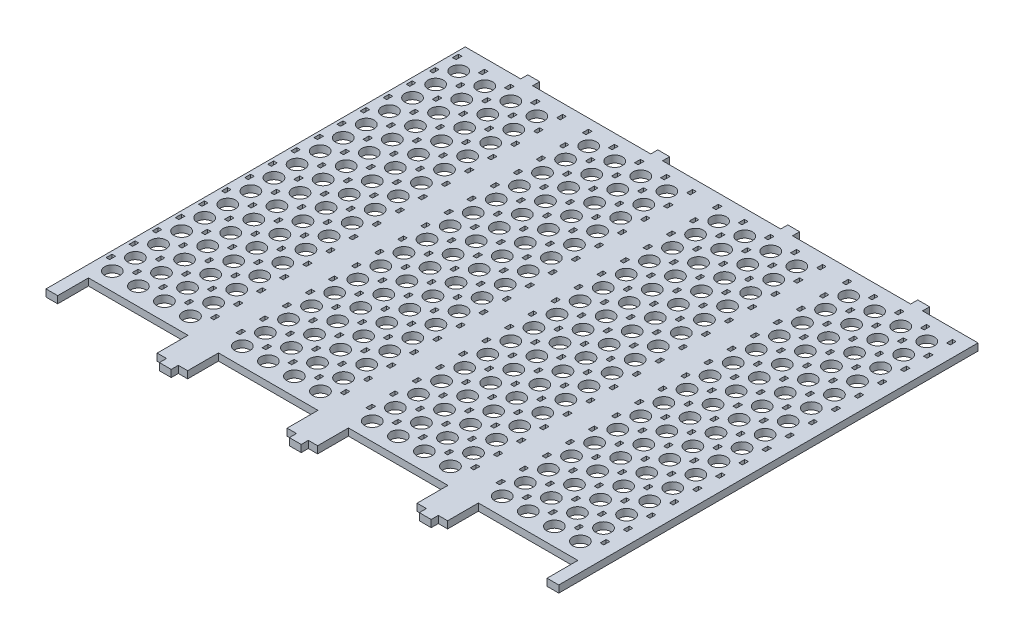
SolidWorks part; units mm, degrees
ref_plane "Front Plane" through (0, 0, 0) normal (0, 0, 1) x (1, 0, 0)
ref_plane "Top Plane" through (0, 0, 0) normal (0, 1, 0) x (1, 0, 0)
ref_plane "Right Plane" through (0, 0, 0) normal (1, 0, 0) x (0, 0, -1)
sketch "Sketch1" plane through (0, 0, 0) normal (0, 1, 0) x (1, 0, 0)
  line L1 (-216.5, -177) -> (216.5, -177)
  line L2 (-216.5, -177) -> (-216.5, 177)
  line L3 (-216.5, 177) -> (216.5, 177)
  line L4 (216.5, -177) -> (216.5, 177)
  line L5 (-216.5, -177) -> (216.5, 177) construction
  line L6 (-216.5, 177) -> (216.5, -177) construction
  point P0 (0, 0)
  dimension "D1" = 354
  dimension "D2" = 433
extrude "Boss-Extrude1" add sketch "Sketch1" along normal blind 6
sketch "Sketch2" plane through (0, 6, 0) normal (0, 1, 0) x (1, 0, 0)
  line L0 (-126.625, -177) -> (-131.125, -177) construction
  line L1 (-198.125, -177) -> (-202.625, -177) construction
  line L2 (-126.625, -177) -> (-131.125, -177)
  line L3 (-198.125, -177) -> (-202.625, -177) construction
  line L4 (-198.125, -177) -> (-131.125, -177) construction
  line L5 (-164.625, -177) -> (-164.625, -151) construction
  line L6 (-122.625, -177) -> (-122.625, -151)
  line L7 (-206.625, -177) -> (-206.625, -151)
  line L8 (-122.625, -177) -> (-206.625, -177)
  line L9 (-122.625, -151) -> (-206.625, -151)
  line M6 (-216.5, -177) -> (216.5, -177)
  dimension "D1" = 26
  dimension "D2" = 42
  dimension "D3" = 42
extrude "Cut-Extrude1" cut sketch "Sketch2" against normal up to next contours L6 L9 L7 M6 region at (-164.625, 6, 164)
pattern_linear "LPattern1" count 4 spacing 109.75 along (1, 0, 0) of "Cut-Extrude1"
sketch "Sketch3" plane through (0, 0, 177) normal (0, 0, 1) x (1, 0, 0)
  line L0 (-122.625, 6) -> (-96.875, 0) construction
  line L1 (-216.5, 6) -> (-206.625, 6) construction
  line L2 (-114.75, 0) -> (-104.75, 0)
  line L3 (-114.75, 0) -> (-114.75, 6)
  line L4 (-114.75, 6) -> (-104.75, 6)
  line L5 (-104.75, 0) -> (-104.75, 6)
  line L6 (-114.75, 0) -> (-104.75, 6) construction
  line L7 (-114.75, 6) -> (-104.75, 0) construction
  point P4 (-109.75, 3)
  dimension "D1" = 10
extrude "Boss-Extrude2" add sketch "Sketch3" along normal blind 6
pattern_linear "LPattern2" count 3 spacing 109.75 along (1, 0, 0) of "Boss-Extrude2"
sketch "Sketch4" plane through (0, 6, 0) normal (0, 1, 0) x (1, 0, 0)
  line L0 (-201.5, -151) -> (-201.5, -112.543) construction
  line L1 (-122.625, -151) -> (-206.625, -151) construction
  line L2 (-216.5, 177) -> (-216.5, -177) construction
  line L3 (-216.5, -136) -> (-147.9325, -136) construction
  circle A0 centre (-201.5, -136) radius 6.5
  circle A1 centre (-179.5, -136) radius 6.5
  circle A2 centre (-157.5, -136) radius 6.5
  circle A3 centre (-135.5, -136) radius 6.5
  circle A4 centre (-179.5, -116.5) radius 6.5
  circle A5 centre (-157.5, -116.5) radius 6.5
  circle A6 centre (-135.5, -116.5) radius 6.5
  circle A7 centre (-179.5, -97) radius 6.5
  circle A8 centre (-157.5, -97) radius 6.5
  circle A9 centre (-135.5, -97) radius 6.5
  circle A10 centre (-179.5, -77.5) radius 6.5
  circle A11 centre (-157.5, -77.5) radius 6.5
  circle A12 centre (-135.5, -77.5) radius 6.5
  circle A13 centre (-179.5, -58) radius 6.5
  circle A14 centre (-157.5, -58) radius 6.5
  circle A15 centre (-135.5, -58) radius 6.5
  circle A16 centre (-179.5, -38.5) radius 6.5
  circle A17 centre (-157.5, -38.5) radius 6.5
  circle A18 centre (-135.5, -38.5) radius 6.5
  circle A19 centre (-179.5, -19) radius 6.5
  circle A20 centre (-157.5, -19) radius 6.5
  circle A21 centre (-135.5, -19) radius 6.5
  circle A22 centre (-179.5, 0.5) radius 6.5
  circle A23 centre (-157.5, 0.5) radius 6.5
  circle A24 centre (-135.5, 0.5) radius 6.5
  circle A25 centre (-179.5, 20) radius 6.5
  circle A26 centre (-157.5, 20) radius 6.5
  circle A27 centre (-135.5, 20) radius 6.5
  circle A28 centre (-179.5, 39.5) radius 6.5
  circle A29 centre (-157.5, 39.5) radius 6.5
  circle A30 centre (-135.5, 39.5) radius 6.5
  circle A31 centre (-179.5, 59) radius 6.5
  circle A32 centre (-157.5, 59) radius 6.5
  circle A33 centre (-135.5, 59) radius 6.5
  circle A34 centre (-179.5, 78.5) radius 6.5
  circle A35 centre (-157.5, 78.5) radius 6.5
  circle A36 centre (-135.5, 78.5) radius 6.5
  circle A37 centre (-179.5, 98) radius 6.5
  circle A38 centre (-157.5, 98) radius 6.5
  circle A39 centre (-135.5, 98) radius 6.5
  circle A40 centre (-179.5, 117.5) radius 6.5
  circle A41 centre (-157.5, 117.5) radius 6.5
  circle A42 centre (-135.5, 117.5) radius 6.5
  circle A43 centre (-179.5, 137) radius 6.5
  circle A44 centre (-157.5, 137) radius 6.5
  circle A45 centre (-135.5, 137) radius 6.5
  circle A46 centre (-179.5, 156.5) radius 6.5
  circle A47 centre (-157.5, 156.5) radius 6.5
  circle A48 centre (-135.5, 156.5) radius 6.5
  circle A49 centre (-201.5, -116.5) radius 6.5
  circle A50 centre (-201.5, -97) radius 6.5
  circle A51 centre (-201.5, -77.5) radius 6.5
  circle A52 centre (-201.5, -58) radius 6.5
  circle A53 centre (-201.5, -38.5) radius 6.5
  circle A54 centre (-201.5, -19) radius 6.5
  circle A55 centre (-201.5, 0.5) radius 6.5
  circle A56 centre (-201.5, 20) radius 6.5
  circle A57 centre (-201.5, 39.5) radius 6.5
  circle A58 centre (-201.5, 59) radius 6.5
  circle A59 centre (-201.5, 78.5) radius 6.5
  circle A60 centre (-201.5, 98) radius 6.5
  circle A61 centre (-201.5, 117.5) radius 6.5
  circle A62 centre (-201.5, 137) radius 6.5
  circle A63 centre (-201.5, 156.5) radius 6.5
  dimension "D2" = 13
  dimension "D1" = 15
  dimension "D3" = 15
  dimension "D4" = 4
  dimension "D5" = 16
extrude "Cut-Extrude2" cut sketch "Sketch4" against normal up to next (6 mm away)
sketch "Sketch5" plane through (0, 6, 0) normal (0, 1, 0) x (1, 0, 0)
  line L0 (-201.5, -116.5) -> (-201.5, -136) construction
  line L1 (-214, -128.75) -> (-211, -128.75)
  line L2 (-214, -128.75) -> (-214, -123.75)
  line L3 (-214, -123.75) -> (-211, -123.75)
  line L4 (-211, -128.75) -> (-211, -123.75)
  line L5 (-214, -128.75) -> (-211, -123.75) construction
  line L6 (-214, -123.75) -> (-211, -128.75) construction
  line L7 (-192, -128.75) -> (-189, -128.75)
  line L8 (-192, -128.75) -> (-192, -123.75)
  line L9 (-192, -123.75) -> (-189, -123.75)
  line L10 (-189, -128.75) -> (-189, -123.75)
  line L11 (-192, -128.75) -> (-189, -123.75) construction
  line L12 (-192, -123.75) -> (-189, -128.75) construction
  line L13 (-170, -128.75) -> (-167, -128.75)
  line L14 (-170, -128.75) -> (-170, -123.75)
  line L15 (-170, -123.75) -> (-167, -123.75)
  line L16 (-167, -128.75) -> (-167, -123.75)
  line L17 (-170, -128.75) -> (-167, -123.75) construction
  line L18 (-170, -123.75) -> (-167, -128.75) construction
  line L19 (-148, -128.75) -> (-145, -128.75)
  line L20 (-148, -128.75) -> (-148, -123.75)
  line L21 (-148, -123.75) -> (-145, -123.75)
  line L22 (-145, -128.75) -> (-145, -123.75)
  line L23 (-148, -128.75) -> (-145, -123.75) construction
  line L24 (-148, -123.75) -> (-145, -128.75) construction
  line L25 (-126, -128.75) -> (-123, -128.75)
  line L26 (-126, -128.75) -> (-126, -123.75)
  line L27 (-126, -123.75) -> (-123, -123.75)
  line L28 (-123, -128.75) -> (-123, -123.75)
  line L29 (-126, -128.75) -> (-123, -123.75) construction
  line L30 (-126, -123.75) -> (-123, -128.75) construction
  line L31 (-192, -109.25) -> (-189, -109.25)
  line L32 (-192, -109.25) -> (-192, -104.25)
  line L33 (-192, -104.25) -> (-189, -104.25)
  line L34 (-189, -109.25) -> (-189, -104.25)
  line L35 (-192, -109.25) -> (-189, -104.25) construction
  line L36 (-192, -104.25) -> (-189, -109.25) construction
  line L37 (-170, -109.25) -> (-167, -109.25)
  line L38 (-170, -109.25) -> (-170, -104.25)
  line L39 (-170, -104.25) -> (-167, -104.25)
  line L40 (-167, -109.25) -> (-167, -104.25)
  line L41 (-170, -109.25) -> (-167, -104.25) construction
  line L42 (-170, -104.25) -> (-167, -109.25) construction
  line L43 (-148, -109.25) -> (-145, -109.25)
  line L44 (-148, -109.25) -> (-148, -104.25)
  line L45 (-148, -104.25) -> (-145, -104.25)
  line L46 (-145, -109.25) -> (-145, -104.25)
  line L47 (-148, -109.25) -> (-145, -104.25) construction
  line L48 (-148, -104.25) -> (-145, -109.25) construction
  line L49 (-126, -109.25) -> (-123, -109.25)
  line L50 (-126, -109.25) -> (-126, -104.25)
  line L51 (-126, -104.25) -> (-123, -104.25)
  line L52 (-123, -109.25) -> (-123, -104.25)
  line L53 (-126, -109.25) -> (-123, -104.25) construction
  line L54 (-126, -104.25) -> (-123, -109.25) construction
  line L55 (-192, -89.75) -> (-189, -89.75)
  line L56 (-192, -89.75) -> (-192, -84.75)
  line L57 (-192, -84.75) -> (-189, -84.75)
  line L58 (-189, -89.75) -> (-189, -84.75)
  line L59 (-192, -89.75) -> (-189, -84.75) construction
  line L60 (-192, -84.75) -> (-189, -89.75) construction
  line L61 (-170, -89.75) -> (-167, -89.75)
  line L62 (-170, -89.75) -> (-170, -84.75)
  line L63 (-170, -84.75) -> (-167, -84.75)
  line L64 (-167, -89.75) -> (-167, -84.75)
  line L65 (-170, -89.75) -> (-167, -84.75) construction
  line L66 (-170, -84.75) -> (-167, -89.75) construction
  line L67 (-148, -89.75) -> (-145, -89.75)
  line L68 (-148, -89.75) -> (-148, -84.75)
  line L69 (-148, -84.75) -> (-145, -84.75)
  line L70 (-145, -89.75) -> (-145, -84.75)
  line L71 (-148, -89.75) -> (-145, -84.75) construction
  line L72 (-148, -84.75) -> (-145, -89.75) construction
  line L73 (-126, -89.75) -> (-123, -89.75)
  line L74 (-126, -89.75) -> (-126, -84.75)
  line L75 (-126, -84.75) -> (-123, -84.75)
  line L76 (-123, -89.75) -> (-123, -84.75)
  line L77 (-126, -89.75) -> (-123, -84.75) construction
  line L78 (-126, -84.75) -> (-123, -89.75) construction
  line L79 (-192, -70.25) -> (-189, -70.25)
  line L80 (-192, -70.25) -> (-192, -65.25)
  line L81 (-192, -65.25) -> (-189, -65.25)
  line L82 (-189, -70.25) -> (-189, -65.25)
  line L83 (-192, -70.25) -> (-189, -65.25) construction
  line L84 (-192, -65.25) -> (-189, -70.25) construction
  line L85 (-170, -70.25) -> (-167, -70.25)
  line L86 (-170, -70.25) -> (-170, -65.25)
  line L87 (-170, -65.25) -> (-167, -65.25)
  line L88 (-167, -70.25) -> (-167, -65.25)
  line L89 (-170, -70.25) -> (-167, -65.25) construction
  line L90 (-170, -65.25) -> (-167, -70.25) construction
  line L91 (-148, -70.25) -> (-145, -70.25)
  line L92 (-148, -70.25) -> (-148, -65.25)
  line L93 (-148, -65.25) -> (-145, -65.25)
  line L94 (-145, -70.25) -> (-145, -65.25)
  line L95 (-148, -70.25) -> (-145, -65.25) construction
  line L96 (-148, -65.25) -> (-145, -70.25) construction
  line L97 (-126, -70.25) -> (-123, -70.25)
  line L98 (-126, -70.25) -> (-126, -65.25)
  line L99 (-126, -65.25) -> (-123, -65.25)
  line L100 (-123, -70.25) -> (-123, -65.25)
  line L101 (-126, -70.25) -> (-123, -65.25) construction
  line L102 (-126, -65.25) -> (-123, -70.25) construction
  line L103 (-192, -50.75) -> (-189, -50.75)
  line L104 (-192, -50.75) -> (-192, -45.75)
  line L105 (-192, -45.75) -> (-189, -45.75)
  line L106 (-189, -50.75) -> (-189, -45.75)
  line L107 (-192, -50.75) -> (-189, -45.75) construction
  line L108 (-192, -45.75) -> (-189, -50.75) construction
  line L109 (-170, -50.75) -> (-167, -50.75)
  line L110 (-170, -50.75) -> (-170, -45.75)
  line L111 (-170, -45.75) -> (-167, -45.75)
  line L112 (-167, -50.75) -> (-167, -45.75)
  line L113 (-170, -50.75) -> (-167, -45.75) construction
  line L114 (-170, -45.75) -> (-167, -50.75) construction
  line L115 (-148, -50.75) -> (-145, -50.75)
  line L116 (-148, -50.75) -> (-148, -45.75)
  line L117 (-148, -45.75) -> (-145, -45.75)
  line L118 (-145, -50.75) -> (-145, -45.75)
  line L119 (-148, -50.75) -> (-145, -45.75) construction
  line L120 (-148, -45.75) -> (-145, -50.75) construction
  line L121 (-126, -50.75) -> (-123, -50.75)
  line L122 (-126, -50.75) -> (-126, -45.75)
  line L123 (-126, -45.75) -> (-123, -45.75)
  line L124 (-123, -50.75) -> (-123, -45.75)
  line L125 (-126, -50.75) -> (-123, -45.75) construction
  line L126 (-126, -45.75) -> (-123, -50.75) construction
  line L127 (-192, -31.25) -> (-189, -31.25)
  line L128 (-192, -31.25) -> (-192, -26.25)
  line L129 (-192, -26.25) -> (-189, -26.25)
  line L130 (-189, -31.25) -> (-189, -26.25)
  line L131 (-192, -31.25) -> (-189, -26.25) construction
  line L132 (-192, -26.25) -> (-189, -31.25) construction
  line L133 (-170, -31.25) -> (-167, -31.25)
  line L134 (-170, -31.25) -> (-170, -26.25)
  line L135 (-170, -26.25) -> (-167, -26.25)
  line L136 (-167, -31.25) -> (-167, -26.25)
  line L137 (-170, -31.25) -> (-167, -26.25) construction
  line L138 (-170, -26.25) -> (-167, -31.25) construction
  line L139 (-148, -31.25) -> (-145, -31.25)
  line L140 (-148, -31.25) -> (-148, -26.25)
  line L141 (-148, -26.25) -> (-145, -26.25)
  line L142 (-145, -31.25) -> (-145, -26.25)
  line L143 (-148, -31.25) -> (-145, -26.25) construction
  line L144 (-148, -26.25) -> (-145, -31.25) construction
  line L145 (-126, -31.25) -> (-123, -31.25)
  line L146 (-126, -31.25) -> (-126, -26.25)
  line L147 (-126, -26.25) -> (-123, -26.25)
  line L148 (-123, -31.25) -> (-123, -26.25)
  line L149 (-126, -31.25) -> (-123, -26.25) construction
  line L150 (-126, -26.25) -> (-123, -31.25) construction
  line L151 (-192, -11.75) -> (-189, -11.75)
  line L152 (-192, -11.75) -> (-192, -6.75)
  line L153 (-192, -6.75) -> (-189, -6.75)
  line L154 (-189, -11.75) -> (-189, -6.75)
  line L155 (-192, -11.75) -> (-189, -6.75) construction
  line L156 (-192, -6.75) -> (-189, -11.75) construction
  line L157 (-170, -11.75) -> (-167, -11.75)
  line L158 (-170, -11.75) -> (-170, -6.75)
  line L159 (-170, -6.75) -> (-167, -6.75)
  line L160 (-167, -11.75) -> (-167, -6.75)
  line L161 (-170, -11.75) -> (-167, -6.75) construction
  line L162 (-170, -6.75) -> (-167, -11.75) construction
  line L163 (-148, -11.75) -> (-145, -11.75)
  line L164 (-148, -11.75) -> (-148, -6.75)
  line L165 (-148, -6.75) -> (-145, -6.75)
  line L166 (-145, -11.75) -> (-145, -6.75)
  line L167 (-148, -11.75) -> (-145, -6.75) construction
  line L168 (-148, -6.75) -> (-145, -11.75) construction
  line L169 (-126, -11.75) -> (-123, -11.75)
  line L170 (-126, -11.75) -> (-126, -6.75)
  line L171 (-126, -6.75) -> (-123, -6.75)
  line L172 (-123, -11.75) -> (-123, -6.75)
  line L173 (-126, -11.75) -> (-123, -6.75) construction
  line L174 (-126, -6.75) -> (-123, -11.75) construction
  line L175 (-192, 7.75) -> (-189, 7.75)
  line L176 (-192, 7.75) -> (-192, 12.75)
  line L177 (-192, 12.75) -> (-189, 12.75)
  line L178 (-189, 7.75) -> (-189, 12.75)
  line L179 (-192, 7.75) -> (-189, 12.75) construction
  line L180 (-192, 12.75) -> (-189, 7.75) construction
  line L181 (-170, 7.75) -> (-167, 7.75)
  line L182 (-170, 7.75) -> (-170, 12.75)
  line L183 (-170, 12.75) -> (-167, 12.75)
  line L184 (-167, 7.75) -> (-167, 12.75)
  line L185 (-170, 7.75) -> (-167, 12.75) construction
  line L186 (-170, 12.75) -> (-167, 7.75) construction
  line L187 (-148, 7.75) -> (-145, 7.75)
  line L188 (-148, 7.75) -> (-148, 12.75)
  line L189 (-148, 12.75) -> (-145, 12.75)
  line L190 (-145, 7.75) -> (-145, 12.75)
  line L191 (-148, 7.75) -> (-145, 12.75) construction
  line L192 (-148, 12.75) -> (-145, 7.75) construction
  line L193 (-126, 7.75) -> (-123, 7.75)
  line L194 (-126, 7.75) -> (-126, 12.75)
  line L195 (-126, 12.75) -> (-123, 12.75)
  line L196 (-123, 7.75) -> (-123, 12.75)
  line L197 (-126, 7.75) -> (-123, 12.75) construction
  line L198 (-126, 12.75) -> (-123, 7.75) construction
  line L199 (-192, 27.25) -> (-189, 27.25)
  line L200 (-192, 27.25) -> (-192, 32.25)
  line L201 (-192, 32.25) -> (-189, 32.25)
  line L202 (-189, 27.25) -> (-189, 32.25)
  line L203 (-192, 27.25) -> (-189, 32.25) construction
  line L204 (-192, 32.25) -> (-189, 27.25) construction
  line L205 (-170, 27.25) -> (-167, 27.25)
  line L206 (-170, 27.25) -> (-170, 32.25)
  line L207 (-170, 32.25) -> (-167, 32.25)
  line L208 (-167, 27.25) -> (-167, 32.25)
  line L209 (-170, 27.25) -> (-167, 32.25) construction
  line L210 (-170, 32.25) -> (-167, 27.25) construction
  line L211 (-148, 27.25) -> (-145, 27.25)
  line L212 (-148, 27.25) -> (-148, 32.25)
  line L213 (-148, 32.25) -> (-145, 32.25)
  line L214 (-145, 27.25) -> (-145, 32.25)
  line L215 (-148, 27.25) -> (-145, 32.25) construction
  line L216 (-148, 32.25) -> (-145, 27.25) construction
  line L217 (-126, 27.25) -> (-123, 27.25)
  line L218 (-126, 27.25) -> (-126, 32.25)
  line L219 (-126, 32.25) -> (-123, 32.25)
  line L220 (-123, 27.25) -> (-123, 32.25)
  line L221 (-126, 27.25) -> (-123, 32.25) construction
  line L222 (-126, 32.25) -> (-123, 27.25) construction
  line L223 (-192, 46.75) -> (-189, 46.75)
  line L224 (-192, 46.75) -> (-192, 51.75)
  line L225 (-192, 51.75) -> (-189, 51.75)
  line L226 (-189, 46.75) -> (-189, 51.75)
  line L227 (-192, 46.75) -> (-189, 51.75) construction
  line L228 (-192, 51.75) -> (-189, 46.75) construction
  line L229 (-170, 46.75) -> (-167, 46.75)
  line L230 (-170, 46.75) -> (-170, 51.75)
  line L231 (-170, 51.75) -> (-167, 51.75)
  line L232 (-167, 46.75) -> (-167, 51.75)
  line L233 (-170, 46.75) -> (-167, 51.75) construction
  line L234 (-170, 51.75) -> (-167, 46.75) construction
  line L235 (-148, 46.75) -> (-145, 46.75)
  line L236 (-148, 46.75) -> (-148, 51.75)
  line L237 (-148, 51.75) -> (-145, 51.75)
  line L238 (-145, 46.75) -> (-145, 51.75)
  line L239 (-148, 46.75) -> (-145, 51.75) construction
  line L240 (-148, 51.75) -> (-145, 46.75) construction
  line L241 (-126, 46.75) -> (-123, 46.75)
  line L242 (-126, 46.75) -> (-126, 51.75)
  line L243 (-126, 51.75) -> (-123, 51.75)
  line L244 (-123, 46.75) -> (-123, 51.75)
  line L245 (-126, 46.75) -> (-123, 51.75) construction
  line L246 (-126, 51.75) -> (-123, 46.75) construction
  line L247 (-192, 66.25) -> (-189, 66.25)
  line L248 (-192, 66.25) -> (-192, 71.25)
  line L249 (-192, 71.25) -> (-189, 71.25)
  line L250 (-189, 66.25) -> (-189, 71.25)
  line L251 (-192, 66.25) -> (-189, 71.25) construction
  line L252 (-192, 71.25) -> (-189, 66.25) construction
  line L253 (-170, 66.25) -> (-167, 66.25)
  line L254 (-170, 66.25) -> (-170, 71.25)
  line L255 (-170, 71.25) -> (-167, 71.25)
  line L256 (-167, 66.25) -> (-167, 71.25)
  line L257 (-170, 66.25) -> (-167, 71.25) construction
  line L258 (-170, 71.25) -> (-167, 66.25) construction
  line L259 (-148, 66.25) -> (-145, 66.25)
  line L260 (-148, 66.25) -> (-148, 71.25)
  line L261 (-148, 71.25) -> (-145, 71.25)
  line L262 (-145, 66.25) -> (-145, 71.25)
  line L263 (-148, 66.25) -> (-145, 71.25) construction
  line L264 (-148, 71.25) -> (-145, 66.25) construction
  line L265 (-126, 66.25) -> (-123, 66.25)
  line L266 (-126, 66.25) -> (-126, 71.25)
  line L267 (-126, 71.25) -> (-123, 71.25)
  line L268 (-123, 66.25) -> (-123, 71.25)
  line L269 (-126, 66.25) -> (-123, 71.25) construction
  line L270 (-126, 71.25) -> (-123, 66.25) construction
  line L271 (-192, 85.75) -> (-189, 85.75)
  line L272 (-192, 85.75) -> (-192, 90.75)
  line L273 (-192, 90.75) -> (-189, 90.75)
  line L274 (-189, 85.75) -> (-189, 90.75)
  line L275 (-192, 85.75) -> (-189, 90.75) construction
  line L276 (-192, 90.75) -> (-189, 85.75) construction
  line L277 (-170, 85.75) -> (-167, 85.75)
  line L278 (-170, 85.75) -> (-170, 90.75)
  line L279 (-170, 90.75) -> (-167, 90.75)
  line L280 (-167, 85.75) -> (-167, 90.75)
  line L281 (-170, 85.75) -> (-167, 90.75) construction
  line L282 (-170, 90.75) -> (-167, 85.75) construction
  line L283 (-148, 85.75) -> (-145, 85.75)
  line L284 (-148, 85.75) -> (-148, 90.75)
  line L285 (-148, 90.75) -> (-145, 90.75)
  line L286 (-145, 85.75) -> (-145, 90.75)
  line L287 (-148, 85.75) -> (-145, 90.75) construction
  line L288 (-148, 90.75) -> (-145, 85.75) construction
  line L289 (-126, 85.75) -> (-123, 85.75)
  line L290 (-126, 85.75) -> (-126, 90.75)
  line L291 (-126, 90.75) -> (-123, 90.75)
  line L292 (-123, 85.75) -> (-123, 90.75)
  line L293 (-126, 85.75) -> (-123, 90.75) construction
  line L294 (-126, 90.75) -> (-123, 85.75) construction
  line L295 (-192, 105.25) -> (-189, 105.25)
  line L296 (-192, 105.25) -> (-192, 110.25)
  line L297 (-192, 110.25) -> (-189, 110.25)
  line L298 (-189, 105.25) -> (-189, 110.25)
  line L299 (-192, 105.25) -> (-189, 110.25) construction
  line L300 (-192, 110.25) -> (-189, 105.25) construction
  line L301 (-170, 105.25) -> (-167, 105.25)
  line L302 (-170, 105.25) -> (-170, 110.25)
  line L303 (-170, 110.25) -> (-167, 110.25)
  line L304 (-167, 105.25) -> (-167, 110.25)
  line L305 (-170, 105.25) -> (-167, 110.25) construction
  line L306 (-170, 110.25) -> (-167, 105.25) construction
  line L307 (-148, 105.25) -> (-145, 105.25)
  line L308 (-148, 105.25) -> (-148, 110.25)
  line L309 (-148, 110.25) -> (-145, 110.25)
  line L310 (-145, 105.25) -> (-145, 110.25)
  line L311 (-148, 105.25) -> (-145, 110.25) construction
  line L312 (-148, 110.25) -> (-145, 105.25) construction
  line L313 (-126, 105.25) -> (-123, 105.25)
  line L314 (-126, 105.25) -> (-126, 110.25)
  line L315 (-126, 110.25) -> (-123, 110.25)
  line L316 (-123, 105.25) -> (-123, 110.25)
  line L317 (-126, 105.25) -> (-123, 110.25) construction
  line L318 (-126, 110.25) -> (-123, 105.25) construction
  line L319 (-192, 124.75) -> (-189, 124.75)
  line L320 (-192, 124.75) -> (-192, 129.75)
  line L321 (-192, 129.75) -> (-189, 129.75)
  line L322 (-189, 124.75) -> (-189, 129.75)
  line L323 (-192, 124.75) -> (-189, 129.75) construction
  line L324 (-192, 129.75) -> (-189, 124.75) construction
  line L325 (-170, 124.75) -> (-167, 124.75)
  line L326 (-170, 124.75) -> (-170, 129.75)
  line L327 (-170, 129.75) -> (-167, 129.75)
  line L328 (-167, 124.75) -> (-167, 129.75)
  line L329 (-170, 124.75) -> (-167, 129.75) construction
  line L330 (-170, 129.75) -> (-167, 124.75) construction
  line L331 (-148, 124.75) -> (-145, 124.75)
  line L332 (-148, 124.75) -> (-148, 129.75)
  line L333 (-148, 129.75) -> (-145, 129.75)
  line L334 (-145, 124.75) -> (-145, 129.75)
  line L335 (-148, 124.75) -> (-145, 129.75) construction
  line L336 (-148, 129.75) -> (-145, 124.75) construction
  line L337 (-126, 124.75) -> (-123, 124.75)
  line L338 (-126, 124.75) -> (-126, 129.75)
  line L339 (-126, 129.75) -> (-123, 129.75)
  line L340 (-123, 124.75) -> (-123, 129.75)
  line L341 (-126, 124.75) -> (-123, 129.75) construction
  line L342 (-126, 129.75) -> (-123, 124.75) construction
  line L343 (-192, 144.25) -> (-189, 144.25)
  line L344 (-192, 144.25) -> (-192, 149.25)
  line L345 (-192, 149.25) -> (-189, 149.25)
  line L346 (-189, 144.25) -> (-189, 149.25)
  line L347 (-192, 144.25) -> (-189, 149.25) construction
  line L348 (-192, 149.25) -> (-189, 144.25) construction
  line L349 (-170, 144.25) -> (-167, 144.25)
  line L350 (-170, 144.25) -> (-170, 149.25)
  line L351 (-170, 149.25) -> (-167, 149.25)
  line L352 (-167, 144.25) -> (-167, 149.25)
  line L353 (-170, 144.25) -> (-167, 149.25) construction
  line L354 (-170, 149.25) -> (-167, 144.25) construction
  line L355 (-148, 144.25) -> (-145, 144.25)
  line L356 (-148, 144.25) -> (-148, 149.25)
  line L357 (-148, 149.25) -> (-145, 149.25)
  line L358 (-145, 144.25) -> (-145, 149.25)
  line L359 (-148, 144.25) -> (-145, 149.25) construction
  line L360 (-148, 149.25) -> (-145, 144.25) construction
  line L361 (-126, 144.25) -> (-123, 144.25)
  line L362 (-126, 144.25) -> (-126, 149.25)
  line L363 (-126, 149.25) -> (-123, 149.25)
  line L364 (-123, 144.25) -> (-123, 149.25)
  line L365 (-126, 144.25) -> (-123, 149.25) construction
  line L366 (-126, 149.25) -> (-123, 144.25) construction
  line L367 (-192, 163.75) -> (-189, 163.75)
  line L368 (-192, 163.75) -> (-192, 168.75)
  line L369 (-192, 168.75) -> (-189, 168.75)
  line L370 (-189, 163.75) -> (-189, 168.75)
  line L371 (-192, 163.75) -> (-189, 168.75) construction
  line L372 (-192, 168.75) -> (-189, 163.75) construction
  line L373 (-170, 163.75) -> (-167, 163.75)
  line L374 (-170, 163.75) -> (-170, 168.75)
  line L375 (-170, 168.75) -> (-167, 168.75)
  line L376 (-167, 163.75) -> (-167, 168.75)
  line L377 (-170, 163.75) -> (-167, 168.75) construction
  line L378 (-170, 168.75) -> (-167, 163.75) construction
  line L379 (-148, 163.75) -> (-145, 163.75)
  line L380 (-148, 163.75) -> (-148, 168.75)
  line L381 (-148, 168.75) -> (-145, 168.75)
  line L382 (-145, 163.75) -> (-145, 168.75)
  line L383 (-148, 163.75) -> (-145, 168.75) construction
  line L384 (-148, 168.75) -> (-145, 163.75) construction
  line L385 (-126, 163.75) -> (-123, 163.75)
  line L386 (-126, 163.75) -> (-126, 168.75)
  line L387 (-126, 168.75) -> (-123, 168.75)
  line L388 (-123, 163.75) -> (-123, 168.75)
  line L389 (-126, 163.75) -> (-123, 168.75) construction
  line L390 (-126, 168.75) -> (-123, 163.75) construction
  line L391 (-214, -109.25) -> (-211, -109.25)
  line L392 (-214, -109.25) -> (-214, -104.25)
  line L393 (-214, -104.25) -> (-211, -104.25)
  line L394 (-211, -109.25) -> (-211, -104.25)
  line L395 (-214, -109.25) -> (-211, -104.25) construction
  line L396 (-214, -104.25) -> (-211, -109.25) construction
  line L397 (-214, -89.75) -> (-211, -89.75)
  line L398 (-214, -89.75) -> (-214, -84.75)
  line L399 (-214, -84.75) -> (-211, -84.75)
  line L400 (-211, -89.75) -> (-211, -84.75)
  line L401 (-214, -89.75) -> (-211, -84.75) construction
  line L402 (-214, -84.75) -> (-211, -89.75) construction
  line L403 (-214, -70.25) -> (-211, -70.25)
  line L404 (-214, -70.25) -> (-214, -65.25)
  line L405 (-214, -65.25) -> (-211, -65.25)
  line L406 (-211, -70.25) -> (-211, -65.25)
  line L407 (-214, -70.25) -> (-211, -65.25) construction
  line L408 (-214, -65.25) -> (-211, -70.25) construction
  line L409 (-214, -50.75) -> (-211, -50.75)
  line L410 (-214, -50.75) -> (-214, -45.75)
  line L411 (-214, -45.75) -> (-211, -45.75)
  line L412 (-211, -50.75) -> (-211, -45.75)
  line L413 (-214, -50.75) -> (-211, -45.75) construction
  line L414 (-214, -45.75) -> (-211, -50.75) construction
  line L415 (-214, -31.25) -> (-211, -31.25)
  line L416 (-214, -31.25) -> (-214, -26.25)
  line L417 (-214, -26.25) -> (-211, -26.25)
  line L418 (-211, -31.25) -> (-211, -26.25)
  line L419 (-214, -31.25) -> (-211, -26.25) construction
  line L420 (-214, -26.25) -> (-211, -31.25) construction
  line L421 (-214, -11.75) -> (-211, -11.75)
  line L422 (-214, -11.75) -> (-214, -6.75)
  line L423 (-214, -6.75) -> (-211, -6.75)
  line L424 (-211, -11.75) -> (-211, -6.75)
  line L425 (-214, -11.75) -> (-211, -6.75) construction
  line L426 (-214, -6.75) -> (-211, -11.75) construction
  line L427 (-214, 7.75) -> (-211, 7.75)
  line L428 (-214, 7.75) -> (-214, 12.75)
  line L429 (-214, 12.75) -> (-211, 12.75)
  line L430 (-211, 7.75) -> (-211, 12.75)
  line L431 (-214, 7.75) -> (-211, 12.75) construction
  line L432 (-214, 12.75) -> (-211, 7.75) construction
  line L433 (-214, 27.25) -> (-211, 27.25)
  line L434 (-214, 27.25) -> (-214, 32.25)
  line L435 (-214, 32.25) -> (-211, 32.25)
  line L436 (-211, 27.25) -> (-211, 32.25)
  line L437 (-214, 27.25) -> (-211, 32.25) construction
  line L438 (-214, 32.25) -> (-211, 27.25) construction
  line L439 (-214, 46.75) -> (-211, 46.75)
  line L440 (-214, 46.75) -> (-214, 51.75)
  line L441 (-214, 51.75) -> (-211, 51.75)
  line L442 (-211, 46.75) -> (-211, 51.75)
  line L443 (-214, 46.75) -> (-211, 51.75) construction
  line L444 (-214, 51.75) -> (-211, 46.75) construction
  line L445 (-214, 66.25) -> (-211, 66.25)
  line L446 (-214, 66.25) -> (-214, 71.25)
  line L447 (-214, 71.25) -> (-211, 71.25)
  line L448 (-211, 66.25) -> (-211, 71.25)
  line L449 (-214, 66.25) -> (-211, 71.25) construction
  line L450 (-214, 71.25) -> (-211, 66.25) construction
  line L451 (-214, 85.75) -> (-211, 85.75)
  line L452 (-214, 85.75) -> (-214, 90.75)
  line L453 (-214, 90.75) -> (-211, 90.75)
  line L454 (-211, 85.75) -> (-211, 90.75)
  line L455 (-214, 85.75) -> (-211, 90.75) construction
  line L456 (-214, 90.75) -> (-211, 85.75) construction
  line L457 (-214, 105.25) -> (-211, 105.25)
  line L458 (-214, 105.25) -> (-214, 110.25)
  line L459 (-214, 110.25) -> (-211, 110.25)
  line L460 (-211, 105.25) -> (-211, 110.25)
  line L461 (-214, 105.25) -> (-211, 110.25) construction
  line L462 (-214, 110.25) -> (-211, 105.25) construction
  line L463 (-214, 124.75) -> (-211, 124.75)
  line L464 (-214, 124.75) -> (-214, 129.75)
  line L465 (-214, 129.75) -> (-211, 129.75)
  line L466 (-211, 124.75) -> (-211, 129.75)
  line L467 (-214, 124.75) -> (-211, 129.75) construction
  line L468 (-214, 129.75) -> (-211, 124.75) construction
  line L469 (-214, 144.25) -> (-211, 144.25)
  line L470 (-214, 144.25) -> (-214, 149.25)
  line L471 (-214, 149.25) -> (-211, 149.25)
  line L472 (-211, 144.25) -> (-211, 149.25)
  line L473 (-214, 144.25) -> (-211, 149.25) construction
  line L474 (-214, 149.25) -> (-211, 144.25) construction
  line L475 (-214, 163.75) -> (-211, 163.75)
  line L476 (-214, 163.75) -> (-214, 168.75)
  line L477 (-214, 168.75) -> (-211, 168.75)
  line L478 (-211, 163.75) -> (-211, 168.75)
  line L479 (-214, 163.75) -> (-211, 168.75) construction
  line L480 (-214, 168.75) -> (-211, 163.75) construction
  line L481 (-201.5, -116.5) -> (-179.5, -136) construction
  point P0 (-212.5, -126.25)
  point P9 (-201.5, -126.25)
  point P11 (-190.5, -126.25)
  point P12 (-190.5, -126.25)
  point P17 (-168.5, -126.25)
  point P22 (-146.5, -126.25)
  point P27 (-124.5, -126.25)
  point P32 (-190.5, -106.75)
  point P37 (-168.5, -106.75)
  point P42 (-146.5, -106.75)
  point P47 (-124.5, -106.75)
  point P52 (-190.5, -87.25)
  point P57 (-168.5, -87.25)
  point P62 (-146.5, -87.25)
  point P67 (-124.5, -87.25)
  point P72 (-190.5, -67.75)
  point P77 (-168.5, -67.75)
  point P82 (-146.5, -67.75)
  point P87 (-124.5, -67.75)
  point P92 (-190.5, -48.25)
  point P97 (-168.5, -48.25)
  point P102 (-146.5, -48.25)
  point P107 (-124.5, -48.25)
  point P112 (-190.5, -28.75)
  point P117 (-168.5, -28.75)
  point P122 (-146.5, -28.75)
  point P127 (-124.5, -28.75)
  point P132 (-190.5, -9.25)
  point P137 (-168.5, -9.25)
  point P142 (-146.5, -9.25)
  point P147 (-124.5, -9.25)
  point P152 (-190.5, 10.25)
  point P157 (-168.5, 10.25)
  point P162 (-146.5, 10.25)
  point P167 (-124.5, 10.25)
  point P172 (-190.5, 29.75)
  point P177 (-168.5, 29.75)
  point P182 (-146.5, 29.75)
  point P187 (-124.5, 29.75)
  point P192 (-190.5, 49.25)
  point P197 (-168.5, 49.25)
  point P202 (-146.5, 49.25)
  point P207 (-124.5, 49.25)
  point P212 (-190.5, 68.75)
  point P217 (-168.5, 68.75)
  point P222 (-146.5, 68.75)
  point P227 (-124.5, 68.75)
  point P232 (-190.5, 88.25)
  point P237 (-168.5, 88.25)
  point P242 (-146.5, 88.25)
  point P247 (-124.5, 88.25)
  point P252 (-190.5, 107.75)
  point P257 (-168.5, 107.75)
  point P262 (-146.5, 107.75)
  point P267 (-124.5, 107.75)
  point P272 (-190.5, 127.25)
  point P277 (-168.5, 127.25)
  point P282 (-146.5, 127.25)
  point P287 (-124.5, 127.25)
  point P292 (-190.5, 146.75)
  point P297 (-168.5, 146.75)
  point P302 (-146.5, 146.75)
  point P307 (-124.5, 146.75)
  point P312 (-190.5, 166.25)
  point P317 (-168.5, 166.25)
  point P322 (-146.5, 166.25)
  point P327 (-124.5, 166.25)
  point P332 (-212.5, -106.75)
  point P337 (-212.5, -87.25)
  point P342 (-212.5, -67.75)
  point P347 (-212.5, -48.25)
  point P352 (-212.5, -28.75)
  point P357 (-212.5, -9.25)
  point P362 (-212.5, 10.25)
  point P367 (-212.5, 29.75)
  point P372 (-212.5, 49.25)
  point P377 (-212.5, 68.75)
  point P382 (-212.5, 88.25)
  point P387 (-212.5, 107.75)
  point P392 (-212.5, 127.25)
  point P397 (-212.5, 146.75)
  point P402 (-212.5, 166.25)
  dimension "D1" = 5
  dimension "D2" = 3
  dimension "D3" = 22
  dimension "D4" = 5
  dimension "D5" = 16
extrude "Cut-Extrude3" cut sketch "Sketch5" against normal up to next (6 mm away)
pattern_linear "LPattern3" count 4 spacing 109.75 along (1, 0, 0) of "Cut-Extrude2", "Cut-Extrude3"
sketch "Sketch6" plane through (0, 0, -177) normal (0, 0, -1) x (-1, 0, 0)
  line L0 (-216.5, 6) -> (216.5, 6) construction
  line L1 (-169.625, 6) -> (-159.625, 6)
  line L2 (-169.625, 6) -> (-169.625, 0)
  line L3 (-169.625, 0) -> (-159.625, 0)
  line L4 (-159.625, 6) -> (-159.625, 0)
  line L5 (-169.625, 6) -> (-169.625, 0) construction
  line L6 (-159.625, 0) -> (-159.625, 6) construction
  line L7 (-216.5, 0) -> (216.5, 0) construction
  line L8 (-59.875, 6) -> (-59.875, 0) construction
  line L9 (-59.875, 6) -> (-49.875, 6)
  line L10 (-59.875, 6) -> (-59.875, 0)
  line L11 (-59.875, 0) -> (-49.875, 0)
  line L12 (-49.875, 6) -> (-49.875, 0)
  line L13 (-49.875, 0) -> (-49.875, 6) construction
  line L14 (49.875, 6) -> (49.875, 0) construction
  line L15 (49.875, 6) -> (59.875, 6)
  line L16 (49.875, 6) -> (49.875, 0)
  line L17 (49.875, 0) -> (59.875, 0)
  line L18 (59.875, 6) -> (59.875, 0)
  line L19 (59.875, 0) -> (59.875, 6) construction
  line L20 (159.625, 6) -> (159.625, 0) construction
  line L21 (159.625, 6) -> (169.625, 6)
  line L22 (159.625, 6) -> (159.625, 0)
  line L23 (159.625, 0) -> (169.625, 0)
  line L24 (169.625, 6) -> (169.625, 0)
  line L25 (169.625, 0) -> (169.625, 6) construction
extrude "Boss-Extrude3" add sketch "Sketch6" along normal blind 6
